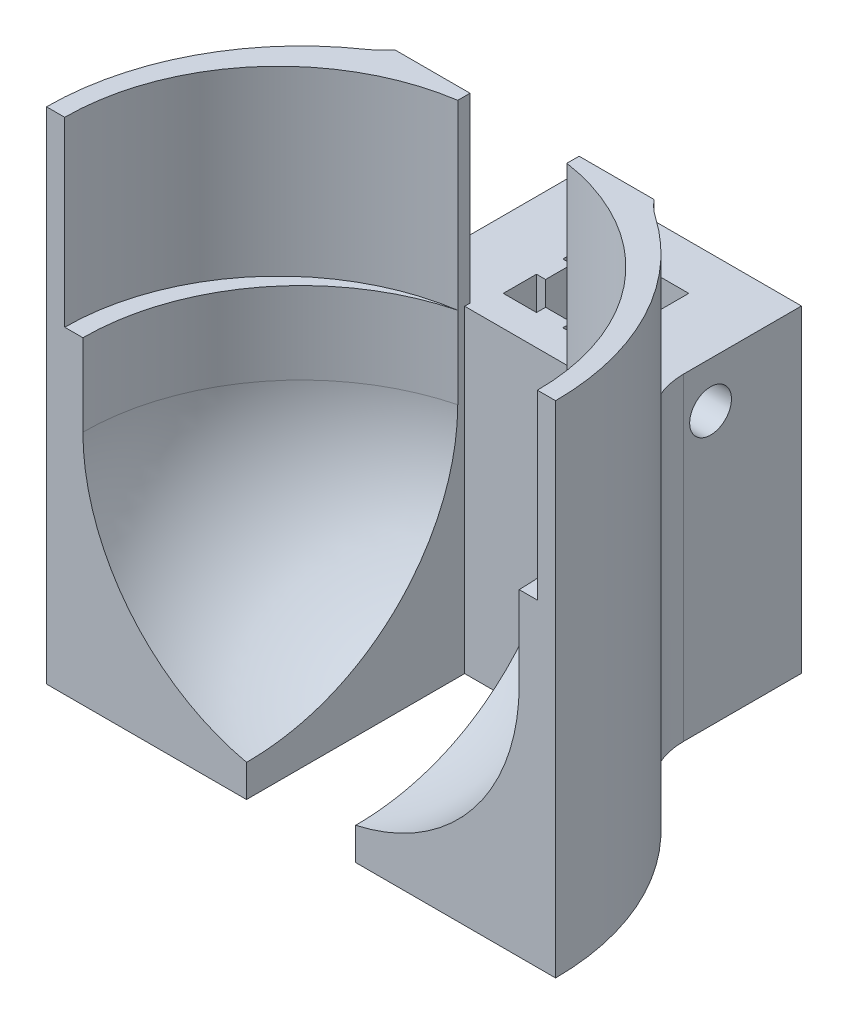
SolidWorks part; units mm, degrees
ref_plane "Front Plane" through (0, 0, 0) normal (0, 0, 1) x (1, 0, 0)
ref_plane "Top Plane" through (0, 0, 0) normal (0, 1, 0) x (1, 0, 0)
ref_plane "Right Plane" through (0, 0, 0) normal (1, 0, 0) x (0, 0, -1)
ref_axis "Axe1" through (0, -1.5691, 0) along (0, 1, 0)
sketch "Esquisse2" plane through (0, 0, 0) normal (-1, 0, 0) x (0, 0, 1)
  line L0 (-24, 35) -> (-28, 35)
  line L1 (-28, 35) -> (-28, 0)
  line L2 (-28, 0) -> (0, 0)
  line L3 (-1, 3) -> (0, 3)
  line L4 (-24, 35) -> (-24, 26)
  line L6 (0, 3) -> (0, 0)
  line L7 (0, -1.5691) -> (0, 32.9511) construction
  arc A0 (-24, 26) -> (-1, 3) centre (-1, 26) ccw
  dimension "D3" = 23
  dimension "D1" = 4
  dimension "D2" = 1
  dimension "D4" = 35
  dimension "D5" = 3
revolve "Révolution1" add sketch "Esquisse2" angle 180 mid plane about axis through (0, -1.5691, 0) along (0, 1, 0)
sketch "Esquisse3" plane through (0, 35, 0) normal (0, -1, 0) x (1, 0, 0)
  line L1 (-6, 0) -> (6, 0)
  line L2 (-6, 0) -> (-6, -24)
  line L3 (-6, -24) -> (6, -24)
  line L4 (6, 0) -> (6, -24)
  line L8 (-6, -27.3496) -> (6, -27.3496)
  line L9 (-6, -27.3496) -> (-6, -28)
  line L10 (-6, -28) -> (6, -28)
  line L11 (6, -27.3496) -> (6, -28)
  arc A0 (-28, 0) -> (28, 0) centre (0, 0) ccw construction
  arc A1 (-24, 0) -> (24, 0) centre (0, 0) ccw construction
  point P6 (0, 0)
  dimension "D1" = 12
extrude "Launcher Hole" cut sketch "Esquisse3" along normal through all
sketch "Esquisse4" plane through (0, 0, 0) normal (0, -1, 0) x (-1, 0, 0)
  line L0 (-6, 27.3496) -> (6, 27.3496) construction
  line L1 (1.45, 27.3496) -> (5.1, 27.3496)
  line L2 (1.45, 27.3496) -> (1.45, 28.3496)
  line L3 (1.45, 28.3496) -> (-1.45, 28.3496)
  line L4 (-1.45, 27.3496) -> (-1.45, 28.3496)
  line L5 (5.1, 27.3496) -> (5.1, 30.9996)
  line L6 (5.1, 30.9996) -> (4.1, 30.9996)
  line L7 (4.1, 30.9996) -> (4.1, 33.8996)
  line L8 (4.1, 33.8996) -> (5.1, 33.8996)
  line L9 (5.1, 33.8996) -> (5.1, 37.5496)
  line L10 (5.1, 37.5496) -> (1.45, 37.5496)
  line L11 (1.45, 37.5496) -> (1.45, 36.5496)
  line L12 (1.45, 36.5496) -> (-1.45, 36.5496)
  line L13 (-1.45, 36.5496) -> (-1.45, 37.5496)
  line L14 (-1.45, 37.5496) -> (-5.1, 37.5496)
  line L15 (-5.1, 37.5496) -> (-5.1, 33.8996)
  line L16 (-5.1, 33.8996) -> (-4.1, 33.8996)
  line L17 (-4.1, 33.8996) -> (-4.1, 30.9996)
  line L18 (-4.1, 30.9996) -> (-5.1, 30.9996)
  line L19 (-5.1, 30.9996) -> (-5.1, 27.3496)
  line L20 (-5.1, 27.3496) -> (-1.45, 27.3496)
  line L21 (5.1, 30.9996) -> (12.5, 30.9996) construction
  line L22 (12.5, 24) -> (-12.5, 24)
  line L23 (12.5, 24) -> (12.5, 42.5496)
  line L24 (12.5, 42.5496) -> (-12.5, 42.5496)
  line L25 (-12.5, 24) -> (-12.5, 42.5496)
  line L26 (-5.1, 30.9996) -> (-12.5, 30.9996) construction
  line L27 (6, 24) -> (-6, 24) construction
  point P7 (0, 27.3496)
  point P40 (0, 28.3496)
  dimension "D1" = 2.9
  dimension "D2" = 1
  dimension "D3" = 10.2
  dimension "D4" = 10.2
  dimension "D5" = 5
  dimension "D6" = 25
extrude "Fixing Support" add sketch "Esquisse4" against normal through all
sketch "Esquisse5" plane through (0, 0, -42.5496) normal (0, 0, -1) x (-1, 0, 0)
  line L3 (0, -1.5691) -> (0, 32.9511) construction
  line L4 (6, 0) -> (-6, 0) construction
  line L5 (6, 35) -> (-6, 35) construction
  circle A0 centre (0, 5) radius 1.6
  circle A1 centre (0, 30) radius 1.6
  dimension "D1" = 3.2
  dimension "D2" = 5
  dimension "D3" = 5
extrude "Fixing Hole" cut sketch "Esquisse5" against normal up to next
sketch "Esquisse7" plane through (0, 0, -42.5496) normal (0, 0, -1) x (-1, 0, 0)
  circle A0 centre (0, 30) radius 4.25
  circle A1 centre (0, 5) radius 4.25
  dimension "D1" = 8.5
extrude "Fixing Screw Hole" cut sketch "Esquisse7" against normal blind 2
sketch "Esquisse6" plane through (-12.5, 0, 0) normal (-1, 0, 0) x (0, 0, 1)
  line L2 (-42.5496, 35) -> (-42.5496, 0) construction
  line L3 (-25.0549, 35) -> (-42.5496, 35) construction
  circle A0 centre (-32.5496, 30) radius 2.3
  dimension "D1" = 4.6
  dimension "D2" = 10
  dimension "D3" = 5
extrude "Ressort Hole" cut sketch "Esquisse6" against normal blind 7
sketch "Esquisse8" plane through (0, 35, 0) normal (0, 1, 0) x (1, 0, 0)
  line L0 (6, 23.2379) -> (6, 24.5879)
  line L1 (6, 24.5879) -> (13.3953, 24.5879)
  line L2 (26, 0) -> (28, 0)
  line L5 (6, 23.2379) -> (6, 0) construction
  line L6 (24, 0) -> (28, 0) construction
  line L7 (6, 0) -> (24, 0) construction
  arc A0 (13.3953, 24.5879) -> (28, 0) centre (0, 0) cw
  arc A1 (26, 0) -> (6, 23.2379) centre (2.5, 0) ccw
  arc A2 (28, 0) -> (12.5, 25.0549) centre (0, 0) ccw construction
  arc A3 (24, 0) -> (6, 23.2379) centre (0, 0) ccw construction
  arc A4 (24, 0) -> (6, 23.2379) centre (0, 0) ccw construction
  dimension "D1" = 1.35
extrude "Boss.-Extru.1" add sketch "Esquisse8" along normal blind 20
mirror "Symétrie1" about plane through (0, 0, 0) normal (1, 0, 0) of "Boss.-Extru.1", "Ressort Hole"
fillet "Congé2" radius 8 2 edges at (-12.5, 17.5, -25.0549) (12.5, 17.5, -25.0549)
